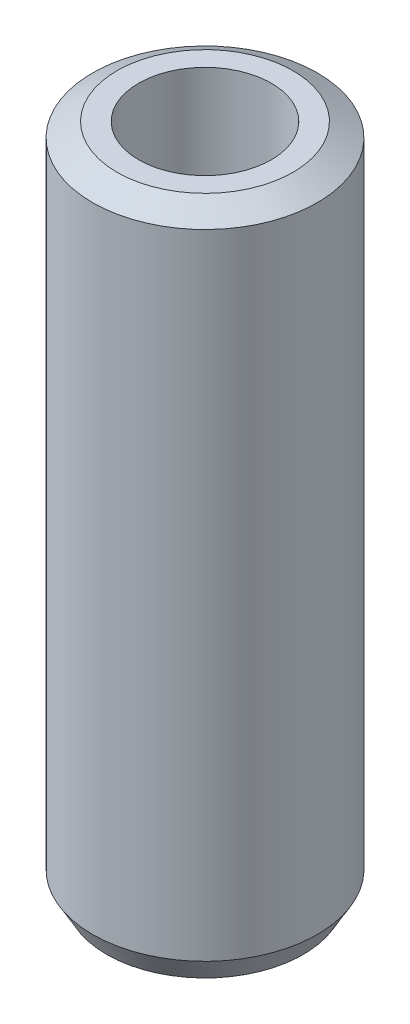
SolidWorks part; units mm, degrees
ref_plane "Front Plane" through (0, 0, 0) normal (0, 0, 1) x (1, 0, 0)
ref_plane "Top Plane" through (0, 0, 0) normal (0, 1, 0) x (1, 0, 0)
ref_plane "Right Plane" through (0, 0, 0) normal (1, 0, 0) x (0, 0, -1)
sketch "Sketch1" plane through (0, 0, 0) normal (0, 1, 0) x (1, 0, 0)
  circle A0 centre (0, 0) radius 27.5
  dimension "SHAFT_OD" = 55
extrude "Boss-Extrude1" add sketch "Sketch1" along normal blind 164.4639
sketch "Sketch2" plane through (0, 0, 0) normal (0, 1, 0) x (1, 0, 0)
  circle A0 centre (0, 0) radius 16.234
  dimension "BORE_D" = 32.468
extrude "Cut-Extrude1" cut sketch "Sketch2" along normal through all
chamfer "Chamfer1" distance 3.4442 angle 60 2 edges at (0, 164.4639, 27.5) (0, 0, 27.5) first distance on face at (0, 164.4639, 27.5) first distance on face at (0, 0, 16.234)
